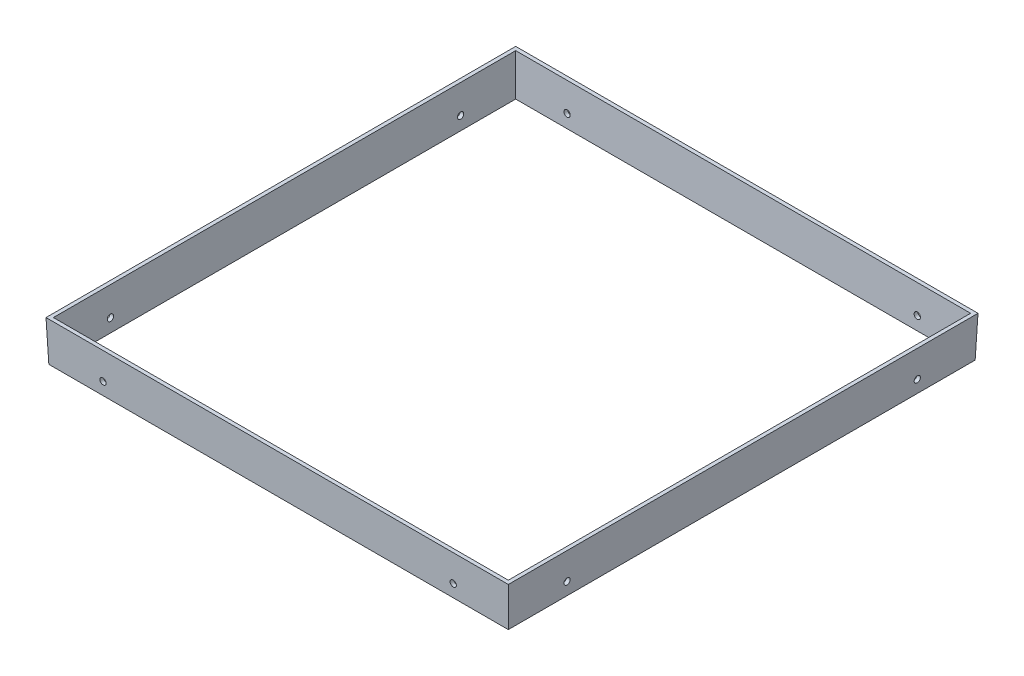
SolidWorks part; units mm, degrees
material "Alumina"
ref_plane "Front Plane" through (0, 0, 0) normal (0, 0, 1) x (1, 0, 0)
ref_plane "Top Plane" through (0, 0, 0) normal (0, 1, 0) x (1, 0, 0)
ref_plane "Right Plane" through (0, 0, 0) normal (1, 0, 0) x (0, 0, -1)
sketch "Sketch2" plane through (0, 0, 0) normal (0, 1, 0) x (1, 0, 0)
  line L0 (-124.65, -126.65) -> (124.65, -126.65)
  line L1 (-124.65, -126.65) -> (-124.65, 126.65)
  line L2 (-124.65, 126.65) -> (124.65, 126.65)
  line L3 (124.65, -126.65) -> (124.65, 126.65)
  line L4 (-124.65, -126.65) -> (124.65, 126.65) construction
  line L5 (-124.65, 126.65) -> (124.65, -126.65) construction
  point P0 (0, 0)
  dimension "D1" = 249.3
  dimension "D2" = 253.3
extrude "Boss-Extrude1" add sketch "Sketch2" along normal blind 22 draft 2 draft outward yes
shell "Shell1" thickness 2 removed face at (0, 0, 0) removed face at (0, 22, 0)
sketch "Sketch4" plane through (124.4982, -4.3476, 0) normal (0.9994, -0.0349, 0) x (0, 0, -1)
  line L0 (0, 79.377) -> (0, -69.6669) construction
  line L1 (-125.417, 26.2938) -> (125.417, 26.2938) construction
  circle A0 centre (-95, 11.2938) radius 1.7
  circle A1 centre (95, 11.2938) radius 1.7
  dimension "D1" = 3.4
  dimension "D2" = 95
  dimension "D3" = 15
extrude "Cut-Extrude1" cut sketch "Sketch4" along direction (1, 0, 0) on the side against the normal blind 292
sketch "Sketch5" plane through (0, -4.4173, -126.4957) normal (0, -0.0349, -0.9994) x (-1, 0, 0)
  line L0 (-123.417, 26.3636) -> (123.417, 26.3636) construction
  line L1 (0, 42.355) -> (0, -57.1183) construction
  circle A0 centre (-95, 11.3636) radius 1.7
  circle A1 centre (95, 11.3636) radius 1.7
  dimension "D1" = 3.4
  dimension "D2" = 95
  dimension "D3" = 15
extrude "Cut-Extrude2" cut sketch "Sketch5" along direction (0, 0, -1) on the side against the normal blind 292
